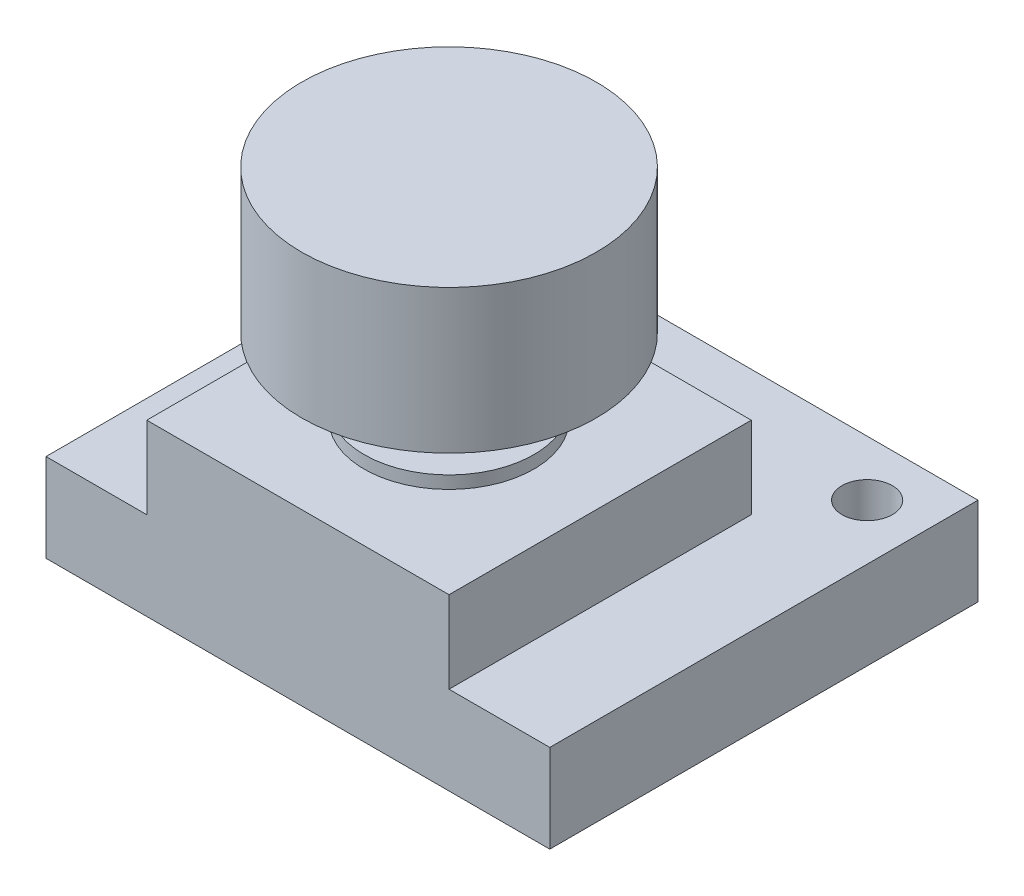
SolidWorks part; units mm, degrees
ref_plane "Front Plane" through (0, 0, 0) normal (0, 0, 1) x (1, 0, 0)
ref_plane "Top Plane" through (0, 0, 0) normal (0, 1, 0) x (1, 0, 0)
ref_plane "Right Plane" through (0, 0, 0) normal (1, 0, 0) x (0, 0, -1)
sketch "Sketch2" plane through (0, 0, 0) normal (0, 1, 0) x (1, 0, 0)
  line L1 (-6, -6) -> (6, -6)
  line L2 (-6, -6) -> (-6, 6)
  line L3 (-6, 6) -> (6, 6)
  line L4 (6, -6) -> (6, 6)
  line L5 (-6, -6) -> (6, 6) construction
  line L6 (-6, 6) -> (6, -6) construction
  point P0 (0, 0)
  dimension "D1" = 12
  dimension "D2" = 12
extrude "Boss-Extrude1" add sketch "Sketch2" along normal blind 3.25
sketch "Sketch3" plane through (0, 3.25, 0) normal (0, 1, 0) x (1, 0, 0)
  line L1 (-1.5, -1.5) -> (1.5, -1.5)
  line L2 (-1.5, -1.5) -> (-1.5, 1.5)
  line L3 (-1.5, 1.5) -> (1.5, 1.5)
  line L4 (1.5, -1.5) -> (1.5, 1.5)
  line L5 (-1.5, -1.5) -> (1.5, 1.5) construction
  line L6 (-1.5, 1.5) -> (1.5, -1.5) construction
  line L7 (1.9, -1.9) -> (-1.9, -1.9)
  line L8 (1.9, -1.9) -> (1.9, 1.9)
  line L9 (1.9, 1.9) -> (-1.9, 1.9)
  line L10 (-1.9, -1.9) -> (-1.9, 1.9)
  line L11 (1.9, -1.9) -> (-1.9, 1.9) construction
  line L12 (1.9, 1.9) -> (-1.9, -1.9) construction
  circle A0 centre (0, 0) radius 3.37
  dimension "D1" = 6.74
  dimension "D2" = 3
  dimension "D3" = 3
  dimension "D4" = 3.8
  dimension "D5" = 3.8
extrude "Boss-Extrude2" add sketch "Sketch3" along normal blind 0.5 contours A0 L7 L10 L9 L8 | L10 L7 L8 L9 L4 L1 L2 L3 region at (0, 3.25, 1.8463) region at (-3.2747, 3.25, 0)
extrude "Boss-Extrude3" add sketch "Sketch3<4>" along normal blind 4 contours L1 L4 L3 L2 region at (0, 3.25, 0)
sketch "Sketch3<4>" plane through (0, 3.25, 0) normal (0, 1, 0) x (1, 0, 0) same geometry as "Sketch3"
extrude "Boss-Extrude4" add sketch "Sketch3<5>" along normal blind 2 from offset 2 contours L10 L7 L8 L9 L4 L1 L2 L3 region at (0, 3.25, 1.8463)
sketch "Sketch3<5>" plane through (0, 3.25, 0) normal (0, 1, 0) x (1, 0, 0) same geometry as "Sketch3"
sketch "Sketch4" plane through (0, 0, 0) normal (0, -1, 0) x (1, 0, 0)
  line L0 (0, 0) -> (0, -2.5) construction
  line L1 (-10, 6) -> (10, 6)
  line L2 (-10, 6) -> (-10, -11)
  line L3 (-10, -11) -> (10, -11)
  line L4 (10, 6) -> (10, -11)
  line L5 (-10, 6) -> (10, -11) construction
  line L6 (-10, -11) -> (10, 6) construction
  line L7 (-6, 6) -> (6, 6) construction
  circle A0 centre (-7.8, -8.8) radius 1
  circle A2 centre (7.8, -8.8) radius 1
  point P4 (0, -2.5)
  dimension "D4" = 2
  dimension "D1" = 20
  dimension "D2" = 17
  dimension "D3" = 1.2
  dimension "D6" = 1.2
extrude "Boss-Extrude5" add sketch "Sketch4" along normal blind 3.5
sketch "Sketch7" plane through (0, 3.25, 0) normal (0, 1, 0) x (1, 0, 0)
  circle A0 centre (0, 0) radius 5.85
  dimension "D1" = 11.7
extrude "Boss-Extrude6" add sketch "Sketch7" along normal blind 5.7 from offset 3
